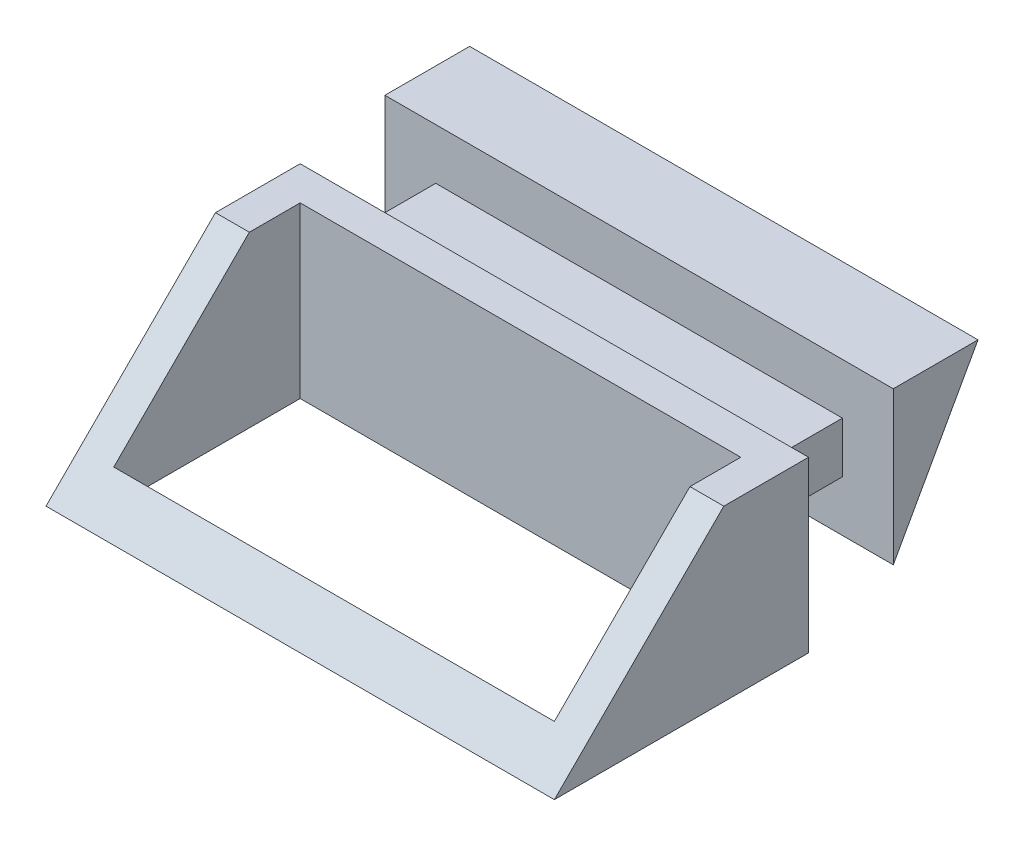
SolidWorks part; units mm, degrees
ref_plane "Front Plane" through (0, 0, 0) normal (0, 0, 1) x (1, 0, 0)
ref_plane "Top Plane" through (0, 0, 0) normal (0, 1, 0) x (1, 0, 0)
ref_plane "Right Plane" through (0, 0, 0) normal (1, 0, 0) x (0, 0, -1)
sketch "Sketch12" plane through (0, 0, 0) normal (0, 1, 0) x (1, 0, 0)
  line L1 (-15, -7.5) -> (15, -7.5)
  line L2 (-15, -7.5) -> (-15, 7.5)
  line L3 (-15, 7.5) -> (15, 7.5)
  line L4 (15, -7.5) -> (15, 7.5)
  line L5 (-15, -7.5) -> (15, 7.5) construction
  line L6 (-15, 7.5) -> (15, -7.5) construction
  point P0 (0, 0)
  dimension "D1" = 15
  dimension "D2" = 30
extrude "Boss-Extrude4" add sketch "Sketch12" along normal blind 10
chamfer "Chamfer1" distance 10 angle 45 1 edges at (0, 10, 7.5)
sketch "Sketch14" plane through (0, 0, -7.5) normal (0, 0, -1) x (-1, 0, 0)
  line L0 (-15, 10) -> (-15, 0) construction
  line L1 (-12, 5) -> (12, 5)
  line L2 (-12, 5) -> (-12, 8)
  line L3 (-12, 8) -> (12, 8)
  line L4 (12, 5) -> (12, 8)
  line L5 (15, 10) -> (15, 0) construction
  line L6 (-15, 10) -> (15, 10) construction
  dimension "D1" = 3
  dimension "D2" = 3
  dimension "D3" = 2
  dimension "D4" = 3
extrude "Boss-Extrude5" add sketch "Sketch14" along normal blind 5
sketch "Sketch15" plane through (0, 0, -12.5) normal (0, 0, -1) x (-1, 0, 0)
  line L0 (-12, 8) -> (-12, 5) construction
  line L1 (-15, 2) -> (15, 2)
  line L2 (-15, 2) -> (-15, 11)
  line L3 (-15, 11) -> (15, 11)
  line L4 (15, 2) -> (15, 11)
  line L5 (-12, 5) -> (12, 5) construction
  line L6 (12, 8) -> (-12, 8) construction
  line L7 (12, 5) -> (12, 8) construction
  dimension "D1" = 3
  dimension "D2" = 3
  dimension "D3" = 3
  dimension "D4" = 3
extrude "Boss-Extrude6" add sketch "Sketch15" along normal blind 5
sketch "Sketch17" plane through (-15, 0, 0) normal (-1, 0, 0) x (0, 0, 1)
  line L0 (-12.5, 2) -> (-17.5, 11)
  line L1 (-17.5, 11) -> (-17.5, 2)
  line L2 (-17.5, 2) -> (-12.5, 2)
extrude "Cut-Extrude10" cut sketch "Sketch17" against normal through all both and the other way through all
sketch "Sketch18" plane through (0, 0, 0) normal (0, -1, 0) x (1, 0, 0)
  line L0 (-15, -7.5) -> (-15, 7.5) construction
  line L1 (-13, -5.5) -> (13, -5.5)
  line L2 (-13, -5.5) -> (-13, 5.5)
  line L3 (-13, 5.5) -> (13, 5.5)
  line L4 (13, -5.5) -> (13, 5.5)
  line L5 (15, -7.5) -> (-15, -7.5) construction
  line L6 (-15, 7.5) -> (15, 7.5) construction
  line L7 (15, 7.5) -> (15, -7.5) construction
  dimension "D1" = 2
  dimension "D2" = 2
  dimension "D3" = 2
  dimension "D4" = 2
extrude "Cut-Extrude11" cut sketch "Sketch18" against normal through all both and the other way through all
